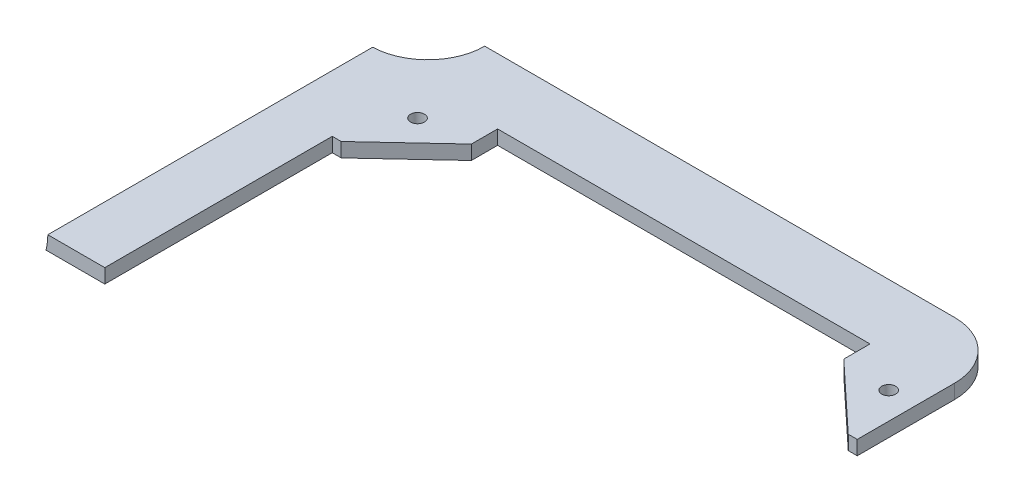
SolidWorks part; units mm, degrees
material "AISI 4130 Steel, annealed at 865C"
ref_plane "X-Y Datum" through (0, 0, 0) normal (0, 0, 1) x (1, 0, 0)
ref_plane "X-Z Datum" through (0, 0, 0) normal (0, 1, 0) x (1, 0, 0)
ref_plane "Y-Z Datum" through (0, 0, 0) normal (1, 0, 0) x (0, 0, -1)
sketch "Sketch1" plane through (0, 0, 0) normal (0, 1, 0) x (1, 0, 0)
  line L1 (-95.25, -38.1) -> (95.25, -38.1)
  line L2 (-95.25, -38.1) -> (-95.25, 38.1)
  line L3 (-95.25, 38.1) -> (95.25, 38.1)
  line L4 (95.25, -38.1) -> (95.25, 38.1)
  line L5 (-95.25, -38.1) -> (95.25, 38.1) construction
  line L6 (-95.25, 38.1) -> (95.25, -38.1) construction
  point P0 (0, 0)
  dimension "D1" = 190.5
  dimension "D2" = 76.2
extrude "Boss-Extrude1" add sketch "Sketch1" along normal blind 3.175 contours L3 L4 L1 L2
sketch "Sketch2" plane through (0, 3.175, 0) normal (0, 1, 0) x (1, 0, 0)
  line L0 (-56.5, 12.6) -> (-41.5, 26.6) construction
  line L1 (-41.5, 26.6) -> (-41.5, 32.45) construction
  line L2 (-41.5, 32.45) -> (41.5, 32.45) construction
  line L3 (41.5, 32.45) -> (41.5, 26.6) construction
  line L4 (-95.25, 38.1) -> (-95.25, -38.1)
  line L5 (-95.25, -38.1) -> (95.25, -38.1)
  line L6 (95.25, -38.1) -> (95.25, 38.1)
  line L7 (95.25, 38.1) -> (-95.25, 38.1)
  line L8 (-95.25, 38.1) -> (-95.25, -38.1)
  line L9 (-95.25, -38.1) -> (95.25, -38.1)
  line L10 (95.25, -38.1) -> (95.25, 38.1)
  line L11 (95.25, 38.1) -> (-95.25, 38.1)
  line L12 (41.5, 26.6) -> (56.5, 12.6) construction
  line L13 (-56.5, 12.6) -> (-41.5, 26.6)
  line L14 (-41.5, 26.6) -> (-41.5, 32.45)
  line L15 (-41.5, 32.45) -> (41.5, 32.45)
  line L16 (41.5, 32.45) -> (41.5, 26.6)
  line L17 (41.5, 26.6) -> (56.5, 12.6)
  line L18 (56.5, 12.6) -> (95.25, 12.6)
  line L19 (-56.5, 12.6) -> (-58.5, 12.6)
  line L20 (58.5, -451.9) -> (58.5, 38.1) construction
  line L21 (58.5, 12.6) -> (58.5, 38.1)
  line L22 (-58.5, 38.1) -> (-58.5, -451.9) construction
  line L23 (-58.5, 38.1) -> (-58.5, -38.1)
  circle A0 centre (-52.5052, 25.6052) radius 1.5453 construction
  circle A1 centre (52.5, 25.6052) radius 1.5453 construction
  circle A2 centre (-52.5052, 25.6052) radius 1.5453
  circle A3 centre (52.5, 25.6052) radius 1.5453
  line M6 (-95.25, -38.1) -> (95.25, -38.1)
  line M7 (95.25, -38.1) -> (95.25, 38.1)
  line M8 (95.25, 38.1) -> (-95.25, 38.1)
  dimension "D1" = 0
extrude "Cut-Extrude4" cut sketch "Sketch2" against normal through all contours L13 L19 L8 L18 L17 L16 L15 L14 M6 M7 | L21 L18 L10 M8 | A2 | A3 | A2 region at (14.8389, 3.175, 6.0761) region at (76.875, 3.175, -25.35) region at (-52.5052, 3.175, -25.6052) region at (52.5, 3.175, -25.6052)
sketch "Sketch3" plane through (0, 0, -38.1) normal (0, 0, -1) x (-1, 0, 0)
  line L4 (95.25, 3.175) -> (-58.5, 3.175)
  line L5 (-58.5, 3.175) -> (-58.5, 0)
  line L6 (-58.5, 0) -> (95.25, 0)
  line L7 (95.25, 0) -> (95.25, 3.175)
  line L8 (95.25, 3.175) -> (-58.5, 3.175)
  line L10 (-58.5, 0) -> (95.25, 0)
  line L11 (95.25, 0) -> (95.25, 3.175)
  line L13 (-58.5, 3.175) -> (-58.5, 0)
  dimension "D1" = 0
extrude "Boss-Extrude2" add sketch "Sketch3" along normal blind 6.35
sketch "Sketch6" plane through (0, 0, 0) normal (0, -1, 0) x (1, 0, 0)
  line L0 (58.5, -44.45) -> (-95.25, -44.45) construction
  line L1 (58.5, -44.45) -> (-95.25, -44.45) construction
  line L14 (58.5, -41.275) -> (-95.25, -41.275) construction
  dimension "D1" = 3.175
sketch "Sketch7" plane through (0, 3.175, 0) normal (0, 1, 0) x (1, 0, 0)
  line L2 (-95.25, 41.275) -> (58.5, 41.275)
  line L3 (-95.25, 41.275) -> (58.5, 41.275) construction
  dimension "D1" = 3.175
sketch3d "3DSketch1"
  line L0 (-83.9, 3.175, 464.7089) -> (-83.9, 3.175, -39.8296)
  line L1 (-83.9, 3.175, -39.8296) -> (-83.9, 3.175, -207.1597)
sweep "Cut-Sweep1" cut path "3DSketch1" circular profile diameter 25.4 parameters "D3"=25.4
sketch "Sketch14" plane through (0, 0, -44.45) normal (0, 0, -1) x (-1, 0, 0)
  line L3 (-58.5, 0) -> (71.6033, 0)
  line L4 (71.2, 3.175) -> (-58.5, 3.175)
  line L5 (-58.5, 3.175) -> (-58.5, 0)
  line L6 (-58.5, 0) -> (71.6033, 0)
  line L7 (71.2, 3.175) -> (-58.5, 3.175)
  line L8 (-58.5, 3.175) -> (-58.5, 0)
  arc A1 (71.2, 3.175) -> (71.6033, 0) centre (83.9, 3.175) ccw
  arc A2 (71.2, 3.175) -> (71.6033, 0) centre (83.9, 3.175) ccw
  dimension "D1" = 0
extrude "Boss-Extrude3" add sketch "Sketch14" along normal blind 2.54
fillet "Fillet1" radius 12.7 1 edges at (58.5, 1.5875, -46.99)
sketch "Sketch13" plane through (0, 0, 0) normal (0, -1, 0) x (-1, 0, 0)
  line L1 (71.6033, -38.1) -> (71.6033, 39.8296) construction
  line L2 (71.6033, 46.99) -> (58.9033, 46.99)
  line L3 (71.6033, 34.29) -> (71.6033, 46.99)
  arc A0 (58.9033, 46.99) -> (71.6033, 34.29) centre (71.6033, 46.99) ccw
  dimension "D1" = 12.7
extrude "Cut-Extrude5" cut sketch "Sketch13" against normal through all
